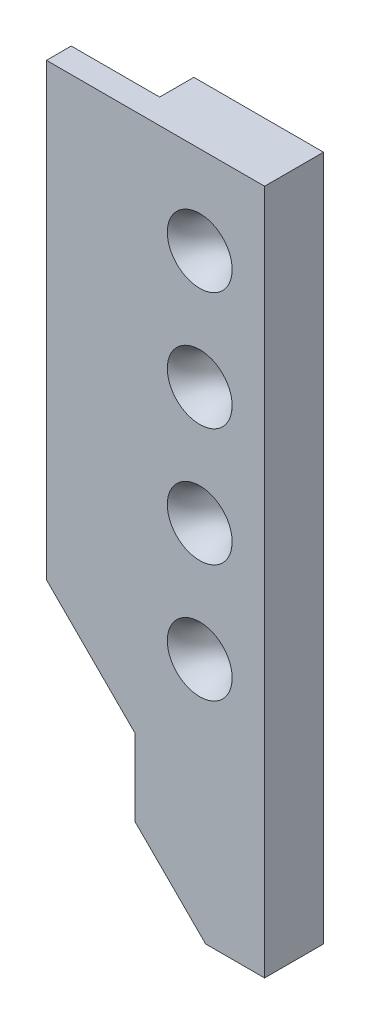
SolidWorks part; units mm, degrees
ref_plane "Front Plane" through (0, 0, 0) normal (0, 0, 1) x (1, 0, 0)
ref_plane "Top Plane" through (0, 0, 0) normal (0, 1, 0) x (1, 0, 0)
ref_plane "Right Plane" through (0, 0, 0) normal (1, 0, 0) x (0, 0, -1)
sketch "Sketch1" plane through (0, 0, 0) normal (0, 0, 1) x (1, 0, 0)
  line L0 (25.2, 31.3209) -> (25.2, -45)
  line L1 (25.2, -45) -> (40.2, -60)
  line L2 (40.2, -60) -> (40.2, 0) construction
  line L3 (40.2, -60) -> (40.2, -85)
  line L5 (62.2, -85) -> (62.2, 31.3209)
  line L6 (62.2, 31.3209) -> (25.2, 31.3209)
  line L12 (40.2, -85) -> (62.2, -85)
  line L13 (40.2, -60) -> (40.2, 31.3209)
  circle A0 centre (0, 0) radius 40.2 construction
  dimension "D1" = 80.4
  dimension "D2" = 15
  dimension "D3" = 15
  dimension "D4" = 60
  dimension "D5" = 25
  dimension "D6" = 22
extrude "Boss-Extrude1" add sketch "Sketch1" along normal blind 4.2 contours L1 L13 L6 L0 | L13 L3 L12 L5 L6 region at (32.9237, -10.7014, 0) region at (51.2, -26.8395, 0)
extrude "Boss-Extrude2" add sketch "Sketch1<3>" against normal blind 5.8 contours L13 L3 L12 L5 L6 region at (51.2, -26.8395, 0)
sketch "Sketch1<3>" plane through (0, 0, 0) normal (0, 0, 1) x (1, 0, 0) same geometry as "Sketch1"
sketch "Sketch2" plane through (0, 0, 4.2) normal (0, 0, 1) x (1, 0, 0)
  line L1 (40.2, -85) -> (62.2, -85) construction
  line L2 (62.2, 31.3209) -> (25.2, 31.3209) construction
  circle A0 centre (51.2, 16.3209) radius 3.5
  point P5 (51.2, -85)
  dimension "D1" = 7
  dimension "D2" = 15
extrude "Cut-Extrude1" cut sketch "Sketch2" against normal up to next
ref_axis "Axis1" through (51.2, 16.3209, -5.8) along (0, 0, 1)
ref_plane "Plane1" through (51.2, 0, 0) normal (-1, 0, 0) x (0, 0, 1)
sketch "Sketch3" plane through (51.2, 0, 0) normal (-1, 0, 0) x (0, 0, 1)
  line L0 (4.2, 31.3209) -> (4.2, -45) construction
  line L1 (-5.8, -85) -> (-5.8, 31.3209) construction
  circle A0 centre (-3.8, 20.0209) radius 0.65
  circle A1 centre (2.2, 20.0209) radius 0.65
  dimension "D1" = 1.3
  dimension "D3" = 2
  dimension "D4" = 2
  dimension "D2" = 0.2
pattern_linear "LPattern1" count 4 spacing 20 along (0, -1, 0) of "Cut-Extrude1"
sketch "Sketch4" plane through (0, 0, 4.2) normal (0, 0, 1) x (1, 0, 0)
  line L0 (52.2, -85) -> (40.2, -73)
  line L1 (40.2, -85) -> (62.2, -85) construction
  line L2 (40.2, -85) -> (40.2, -60) construction
  line L3 (40.2, -73) -> (40.2, -85)
  line L4 (40.2, -85) -> (52.2, -85)
  dimension "D1" = 10
  dimension "D2" = 45
extrude "Cut-Extrude2" cut sketch "Sketch4" against normal up to next
ref_plane "Plane2" through (25.2, -45, 0) normal (0, -1, 0) x (-1, 0, 0)
sketch "Sketch6" plane through (25.2, 0, 0) normal (-1, 0, 0) x (0, 0, 1)
  line L0 (4.2, -45) -> (0, -45)
  line L1 (-20.9883, -45) -> (20.9883, -45) construction
  line L2 (4.2, -45) -> (4.2, -60) construction
  line L3 (0, -45) -> (3.7, -60)
  line L4 (4.2, -60) -> (0, -60) construction
  line L5 (3.7, -60) -> (4.2, -60)
  line L6 (4.2, -60) -> (4.2, -45)
  line L8 (4.2, -45) -> (0, -45)
  line L9 (4.2, -45) -> (4.2, -60)
  line L10 (4.2, -60) -> (0, -60)
  line L11 (0, -45) -> (0, -60)
  dimension "D1" = 0.5
extrude "Cut-Extrude3" cut sketch "Sketch6" against normal up to surface (15 mm away) contours L3 L11 L10 region at (25.2, -55, 1.2333) up to face at (40.2, -33.893, -0.5333)
ref_plane "Plane3" through (25.5117, -18.7086, 0) normal (0.8064, -0.5914, 0) x (0, 0, -1)
sketch "Sketch9" plane through (25.5117, -18.7086, 0) normal (0.8064, -0.5914, 0) x (0, 0, -1)
  line L1 (-2.8, 46.9391) -> (-0.6, 46.9391) construction
  line L2 (5.8, 46.9391) -> (-4.2, 46.9391) construction
  line L3 (-4.2, -31.7616) -> (-4.2, 62.0402) construction
  line L5 (-2.9, 47.4187) -> (-0.5, 47.4187) construction
  line L6 (-0.5, 47.4187) -> (-2.9, 47.4187)
  arc A0 (-2.9, 47.4187) -> (-0.5, 47.4187) centre (-1.7, 47.4187) ccw
  point P11 (-1.7, 47.4187)
  dimension "D1" = 2.4
  dimension "D2" = 2.2
  dimension "D3" = 2.5
revolve "Cut-Revolve4" [suppressed] cut sketch "Sketch9" angle 360 about L6
pattern_circular "CirPattern1" [suppressed] count 4 over 360 about axis through (51.2, 16.3209, -5.8) along (0, 0, 1) of bodies 108
pattern_linear "LPattern2" [suppressed] count 4 spacing 20 count 2 spacing 5 of bodies 109
sketch "Sketch10" plane through (51.2, 0, 0) normal (-1, 0, 0) x (0, 0, 1)
  line L0 (-5.8, -73) -> (-5.8, 31.3209) construction
  line L1 (4.2, 31.3209) -> (4.2, -45) construction
  line L2 (4.2, 21.8209) -> (4.2, 19.8209)
  line L3 (4.2, 19.8209) -> (-5.8, 19.8209)
  line L4 (-5.8, 19.8209) -> (-5.8, 21.8209)
  arc A0 (-5.8, 21.8209) -> (4.2, 21.8209) centre (-0.8, 27.0709) ccw
  dimension "D1" = 2
revolve "Cut-Revolve5" cut sketch "Sketch10" angle 360 about axis through (51.2, 16.3209, -5.8) along (0, 0, 1) region at (51.2, 20.4035, -4.5871) region at (51.2, 20.4035, 2.9871)
pattern_linear "LPattern3" count 4 spacing 20 along (0, -1, 0) of "Cut-Revolve5"
